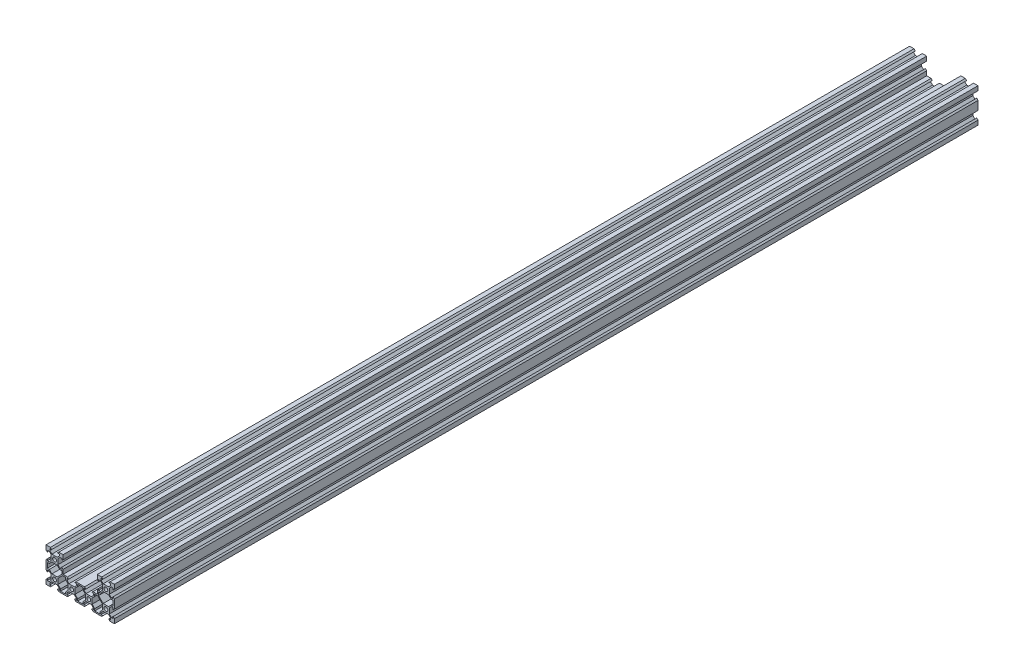
SolidWorks part; units mm, degrees
ref_plane "Front Plane" through (0, 0, 0) normal (0, 0, 1) x (1, 0, 0)
ref_plane "Top Plane" through (0, 0, 0) normal (0, 1, 0) x (1, 0, 0)
ref_plane "Right Plane" through (0, 0, 0) normal (1, 0, 0) x (0, 0, -1)
sketch "Sketch2" plane through (0, 0, 0) normal (0, 0, 1) x (1, 0, 0)
  line L0 (0, 10) -> (0, -10) construction
  line L1 (0, -10) -> (-40, -10)
  line L2 (-40, -10) -> (-40, 30)
  line L3 (-40, 30) -> (-20, 30)
  line L4 (-20, 30) -> (-20, 10)
  line L5 (-20, 10) -> (0, 10)
  line L6 (-20, 10) -> (-40, -10) construction
  line L7 (-20, 10) -> (0, -10) construction
  line L8 (0, 10) -> (-20, -10) construction
  line L9 (-20, -10) -> (-40, 10) construction
  line L10 (-40, 10) -> (-20, 30) construction
  line L11 (-20, 30) -> (-19.842, 30.1306) construction
  line L12 (-40, 30) -> (-20, 10) construction
  line L13 (-35.5, 28.5) -> (-35.5, 25.5)
  line L14 (-40, 24.875) -> (-38.5, 23.375)
  line L15 (-40, 20) -> (-20, 20) construction
  line L16 (-40, 15.125) -> (-38.5, 16.625)
  line L17 (-30, 30) -> (-30, -10) construction
  line L18 (-33.375, 28.5) -> (-35.5, 28.5)
  line L19 (-38.5, 25.5) -> (-35.5, 25.5)
  line L20 (-34.875, 30) -> (-33.375, 28.5)
  line L21 (-38.5, 23.375) -> (-38.5, 25.5)
  line L22 (-38.5, 16.625) -> (-38.5, 14.5)
  line L23 (-38.5, 14.5) -> (-35.5, 14.5)
  line L24 (-25.125, 30) -> (-26.625, 28.5)
  line L25 (-26.625, 28.5) -> (-24.5, 28.5)
  line L26 (-20, 24.875) -> (-21.5, 23.375)
  line L27 (-21.5, 23.375) -> (-21.5, 25.5)
  line L28 (-21.5, 25.5) -> (-24.5, 25.5)
  line L29 (-24.5, 28.5) -> (-24.5, 25.5)
  line L30 (-20, 15.125) -> (-21.5, 16.625)
  line L31 (-21.5, 16.625) -> (-21.5, 14.5)
  line L32 (-21.5, 14.5) -> (-24.5, 14.5)
  line L33 (-40, 4.875) -> (-38.5, 3.375)
  line L34 (-38.5, 3.375) -> (-38.5, 5.5)
  line L35 (-38.5, 5.5) -> (-35.5, 5.5)
  line L36 (-25.125, -10) -> (-26.625, -8.5)
  line L37 (-26.625, -8.5) -> (-24.5, -8.5)
  line L38 (-24.5, -8.5) -> (-24.5, -5.5)
  line L39 (-34.875, -10) -> (-33.375, -8.5)
  line L40 (-35.5, -8.5) -> (-35.5, -5.5)
  line L41 (-33.375, -8.5) -> (-35.5, -8.5)
  line L42 (-40, -4.875) -> (-38.5, -3.375)
  line L43 (-38.5, -3.375) -> (-38.5, -5.5)
  line L44 (-38.5, -5.5) -> (-35.5, -5.5)
  line L45 (-26, 24) -> (-34, 24)
  line L46 (-26, 24) -> (-26, 16)
  line L47 (-34, 24) -> (-34, 16)
  line L48 (-34, 16) -> (-26, 16)
  line L49 (-35.5, 26.3839) -> (-33.1161, 24)
  line L50 (-36.3839, 25.5) -> (-34, 23.1161)
  line L51 (-23.6161, 25.5) -> (-26, 23.1161)
  line L52 (-24.5, 26.3839) -> (-26.8839, 24)
  line L53 (-23.6161, 14.5) -> (-26, 16.8839)
  line L54 (-38.5, 13) -> (-38.5, 7)
  line L55 (-38.5, 13) -> (-36.1161, 13)
  line L56 (-36.3839, 14.5) -> (-34, 16.8839)
  line L57 (-36.1161, 13) -> (-33.1161, 16)
  line L58 (-38.5, 7) -> (-36.1161, 7)
  line L59 (-36.1161, 7) -> (-33.1161, 4)
  line L60 (-26, -4) -> (-34, -4)
  line L61 (-34, -4) -> (-34, 4)
  line L62 (-26, -4) -> (-26, 4)
  line L63 (-34, 4) -> (-26, 4)
  line L64 (-26.891, 4) -> (-21.5, 9.391)
  line L65 (-23.8839, 13) -> (-26.8839, 16)
  line L66 (-21.5, 13) -> (-23.8839, 13)
  line L67 (-21.5, 13) -> (-21.5, 9.391)
  line L68 (-23, -6.1161) -> (-26, -3.1161)
  line L69 (-23, -8.5) -> (-23, -6.1161)
  line L70 (-17, -8.5) -> (-23, -8.5)
  line L71 (-17, -8.5) -> (-17, -6.1161)
  line L72 (-17, -6.1161) -> (-14, -3.1161)
  line L73 (-17, 6.1161) -> (-14, 3.1161)
  line L74 (-17, 8.5) -> (-17, 6.1161)
  line L75 (-17, 8.5) -> (-20.609, 8.5)
  line L76 (-26, 3.109) -> (-20.609, 8.5)
  line L77 (-36.3839, 5.5) -> (-34, 3.1161)
  line L78 (-36.3839, -5.5) -> (-34, -3.1161)
  line L79 (-35.5, -6.3839) -> (-33.1161, -4)
  line L80 (-24.5, -6.3839) -> (-26.8839, -4)
  line L81 (-5.125, 10) -> (-6.625, 8.5)
  line L82 (-4.5, 8.5) -> (-4.5, 5.5)
  line L83 (-6.625, 8.5) -> (-4.5, 8.5)
  line L84 (-4.5, 6.3839) -> (-6.8839, 4)
  line L85 (14.875, -10) -> (13.375, -8.5)
  line L86 (-15.5, -8.5) -> (-15.5, -5.5)
  line L87 (-14.875, -10) -> (-13.375, -8.5)
  line L88 (-13.375, -8.5) -> (-15.5, -8.5)
  line L89 (13.375, -8.5) -> (15.5, -8.5)
  line L90 (15.5, -8.5) -> (15.5, -5.5)
  line L91 (-5.125, -10) -> (-6.625, -8.5)
  line L92 (-6.625, -8.5) -> (-4.5, -8.5)
  line L93 (-4.5, -8.5) -> (-4.5, -5.5)
  line L94 (-15.5, -6.3839) -> (-13.1161, -4)
  line L95 (15.5, -6.3839) -> (13.1161, -4)
  line L96 (4.5, -6.3839) -> (6.8839, -4)
  line L97 (-4.5, -6.3839) -> (-6.8839, -4)
  line L98 (-6, -4) -> (-6, 4)
  line L99 (-14, -4) -> (-6, -4)
  line L100 (-14, -4) -> (-14, 4)
  line L101 (-6, 4) -> (-14, 4)
  line L102 (0, 0) -> (-40, 0) construction
  line L103 (-15.5, 6.3839) -> (-13.1161, 4)
  line L104 (-15.5, 8.5) -> (-15.5, 5.5)
  line L105 (-14.875, 10) -> (-13.375, 8.5)
  line L106 (-13.375, 8.5) -> (-15.5, 8.5)
  line L107 (-10, 10) -> (-10, -10) construction
  line L108 (4.5, -8.5) -> (4.5, -5.5)
  line L109 (6.625, -8.5) -> (4.5, -8.5)
  line L110 (5.125, -10) -> (6.625, -8.5)
  line L111 (17, 8.5) -> (20.609, 8.5)
  line L112 (17, 8.5) -> (17, 6.1161)
  line L113 (17, 6.1161) -> (14, 3.1161)
  line L114 (15.5, 6.3839) -> (13.1161, 4)
  line L115 (14.875, 10) -> (13.375, 8.5)
  line L116 (15.5, 8.5) -> (15.5, 5.5)
  line L117 (13.375, 8.5) -> (15.5, 8.5)
  line L118 (5.125, 10) -> (6.625, 8.5)
  line L119 (6.625, 8.5) -> (4.5, 8.5)
  line L120 (4.5, 8.5) -> (4.5, 5.5)
  line L121 (4.5, 6.3839) -> (6.8839, 4)
  line L122 (14, -4) -> (6, -4)
  line L123 (14, -4) -> (14, 4)
  line L124 (6, 4) -> (14, 4)
  line L125 (6, -4) -> (6, 4)
  line L126 (0, -10) -> (40, -10)
  line L127 (36.3839, 14.5) -> (34, 16.8839)
  line L128 (40, 15.125) -> (38.5, 16.625)
  line L129 (38.5, 16.625) -> (38.5, 14.5)
  line L130 (38.5, 14.5) -> (35.5, 14.5)
  line L131 (38.5, 7) -> (36.1161, 7)
  line L132 (38.5, 13) -> (38.5, 7)
  line L133 (40, 4.875) -> (38.5, 3.375)
  line L134 (38.5, 3.375) -> (38.5, 5.5)
  line L135 (38.5, 5.5) -> (35.5, 5.5)
  line L136 (36.3839, 5.5) -> (34, 3.1161)
  line L137 (36.1161, 7) -> (33.1161, 4)
  line L138 (38.5, 13) -> (36.1161, 13)
  line L139 (36.1161, 13) -> (33.1161, 16)
  line L140 (26, 24) -> (34, 24)
  line L141 (34, 24) -> (34, 16)
  line L142 (34, 16) -> (26, 16)
  line L143 (26, 24) -> (26, 16)
  line L144 (23.6161, 14.5) -> (26, 16.8839)
  line L145 (21.5, 16.625) -> (21.5, 14.5)
  line L146 (20, 15.125) -> (21.5, 16.625)
  line L147 (21.5, 14.5) -> (24.5, 14.5)
  line L148 (23.8839, 13) -> (26.8839, 16)
  line L149 (21.5, 13) -> (23.8839, 13)
  line L150 (21.5, 13) -> (21.5, 9.391)
  line L151 (26.891, 4) -> (21.5, 9.391)
  line L152 (26, 3.109) -> (20.609, 8.5)
  line L153 (38.5, -3.375) -> (38.5, -5.5)
  line L154 (40, -4.875) -> (38.5, -3.375)
  line L155 (36.3839, -5.5) -> (34, -3.1161)
  line L156 (38.5, -5.5) -> (35.5, -5.5)
  line L157 (35.5, -6.3839) -> (33.1161, -4)
  line L158 (35.5, -8.5) -> (35.5, -5.5)
  line L159 (34.875, -10) -> (33.375, -8.5)
  line L160 (33.375, -8.5) -> (35.5, -8.5)
  line L161 (34, 4) -> (26, 4)
  line L162 (34, -4) -> (34, 4)
  line L163 (26, -4) -> (34, -4)
  line L164 (26, -4) -> (26, 4)
  line L165 (23, -6.1161) -> (26, -3.1161)
  line L166 (23, -8.5) -> (23, -6.1161)
  line L167 (26.625, -8.5) -> (24.5, -8.5)
  line L168 (24.5, -8.5) -> (24.5, -5.5)
  line L169 (24.5, -6.3839) -> (26.8839, -4)
  line L170 (17, -6.1161) -> (14, -3.1161)
  line L171 (17, -8.5) -> (17, -6.1161)
  line L172 (17, -8.5) -> (23, -8.5)
  line L173 (40, -10) -> (40, 30)
  line L174 (36.3839, 25.5) -> (34, 23.1161)
  line L175 (35.5, 26.3839) -> (33.1161, 24)
  line L176 (40, 24.875) -> (38.5, 23.375)
  line L177 (38.5, 23.375) -> (38.5, 25.5)
  line L178 (38.5, 25.5) -> (35.5, 25.5)
  line L179 (35.5, 28.5) -> (35.5, 25.5)
  line L180 (33.375, 28.5) -> (35.5, 28.5)
  line L181 (34.875, 30) -> (33.375, 28.5)
  line L182 (25.125, 30) -> (26.625, 28.5)
  line L183 (26.625, 28.5) -> (24.5, 28.5)
  line L184 (24.5, 26.3839) -> (26.8839, 24)
  line L185 (24.5, 28.5) -> (24.5, 25.5)
  line L186 (23.6161, 25.5) -> (26, 23.1161)
  line L187 (21.5, 25.5) -> (24.5, 25.5)
  line L188 (21.5, 23.375) -> (21.5, 25.5)
  line L189 (20, 24.875) -> (21.5, 23.375)
  line L190 (40, 30) -> (20, 30)
  line L191 (0, 10) -> (20, 10)
  line L192 (20, 10) -> (20, 30)
  line L193 (3, 8.5) -> (-3, 8.5)
  line L194 (-3, 8.5) -> (-3, 6.1161)
  line L195 (-3, 6.1161) -> (-6, 3.1161)
  line L196 (3, 8.5) -> (3, 6.1161)
  line L197 (3, 6.1161) -> (6, 3.1161)
  line L198 (-3, -8.5) -> (-3, -6.1161)
  line L199 (-3, -6.1161) -> (-6, -3.1161)
  line L200 (3, -6.1161) -> (6, -3.1161)
  line L201 (3, -8.5) -> (3, -6.1161)
  line L202 (3, -8.5) -> (-3, -8.5)
  line L203 (25.125, -10) -> (26.625, -8.5)
  circle A0 centre (-30, 20) radius 2.25
  circle A1 centre (-30, 0) radius 2.25
  circle A2 centre (-10, 0) radius 2.25
  circle A3 centre (10, 0) radius 2.25
  circle A4 centre (30, 20) radius 2.25
  circle A5 centre (30, 0) radius 2.25
  point P3 (0, 0)
  point P75 (-38.5, 10)
  point P232 (25.125, -10)
  point P271 (0, 8.5)
  dimension "D8" = 4.5
  dimension "D1" = 40
  dimension "D2" = 40
  dimension "D3" = 20
  dimension "D4" = 4.5
  dimension "D5" = 3.375
  dimension "D6" = 1.5
  dimension "D7" = 8
  dimension "D9" = 0.625
  dimension "D10" = 0.625
  dimension "D11" = 1.5
  dimension "D12" = 0.63
  dimension "D13" = 40
  dimension "D14" = 40
  dimension "D15" = 20
  dimension "D16" = 3
  dimension "D17" = 1.5
  dimension "D18" = 0.625
extrude "Boss-Extrude1" add sketch "Sketch2" along normal blind 1010 contours L140 L143 L142 L141 A4 | L173 L190 L181 L180 L179 L178 L177 L176 | L133 L173 L128 L129 L130 L127 L141 L142 L139 L138 L132 L131 L137 L161 L162 L136 L135 L134 | L179 L175 L140 L141 L174 L178 | L187 L186 L143 L140 L184 L185 | L192 L189 L188 L187 L185 L183 L182 L190 | L192 L191 L115 L117 L116 L114 L124 L123 L113 L112 L111 L152 L164 L161 L151 L150 L149 L148 L142 L143 L144 L147 L145 L146 | L164 L163 L162 L161 A5 | L126 L173 L154 L153 L156 L158 L160 L159 | L163 L157 L158 L156 L155 L162 | L126 L203 L167 L168 L169 L163 L164 L165 L166 L172 L171 L170 L123 L122 L95 L90 L89 L85 | L125 L122 L123 L124 A3 | L201 L202 L198 L199 L98 L99 L97 L93 L92 L91 L1 L126 L110 L109 L108 L96 L122 L125 L200 | L196 L197 L125 L124 L121 L120 L119 L118 L191 L5 L81 L83 L82 L84 L101 L98 L195 L194 L193 | L98 L101 L100 L99 A2 | L99 L100 L72 L71 L70 L69 L68 L62 L60 L80 L38 L37 L36 L1 L87 L88 L86 L94 | L106 L105 L5 L4 L30 L31 L32 L53 L46 L48 L65 L66 L67 L64 L63 L62 L76 L75 L74 L73 L100 L101 L103 L104 | L63 L61 L60 L62 A1 | L40 L79 L60 L61 L78 L44 | L44 L43 L42 L2 L1 L39 L41 L40 | L77 L61 L63 L59 L58 L54 L55 L57 L48 L47 L56 L23 L22 L16 L2 L33 L34 L35 | L47 L48 L46 L45 A0 | L25 L29 L28 L27 L26 L4 L3 L24 | L14 L21 L19 L13 L18 L20 L3 L2 | L29 L52 L45 L46 L51 L28 | L19 L50 L47 L45 L49 L13 region at (-2.5625, -9.8461, 0) region at (-20, -9.8461, 0) region at (14.2338, -9.1412, 0) region at (-37.6111, -7.6111, 0) region at (37.6111, -7.6111, 0) region at (-10, -3.8869, 0) region at (6.4419, -3.8869, 0) region at (-39.8461, 10, 0) region at (-34.75, -4.75, 0) region at (-30, -3.8869, 0) region at (39.1412, 4.2338, 0) region at (34.75, -4.75, 0) region at (26.4419, -3.8869, 0) region at (-5.8461, 3.5581, 0) region at (-37.6111, 27.6111, 0) region at (-20.272, 9.728, 0) region at (20.272, 9.728, 0) region at (37.6111, 27.6111, 0) region at (-22.3889, 27.6111, 0) region at (-34.75, 24.75, 0) region at (-33.8869, 20, 0) region at (33.8869, 16.4419, 0) region at (22.3889, 27.6111, 0) region at (34.75, 24.75, 0) region at (-25.25, 24.75, 0) region at (25.25, 24.75, 0)
